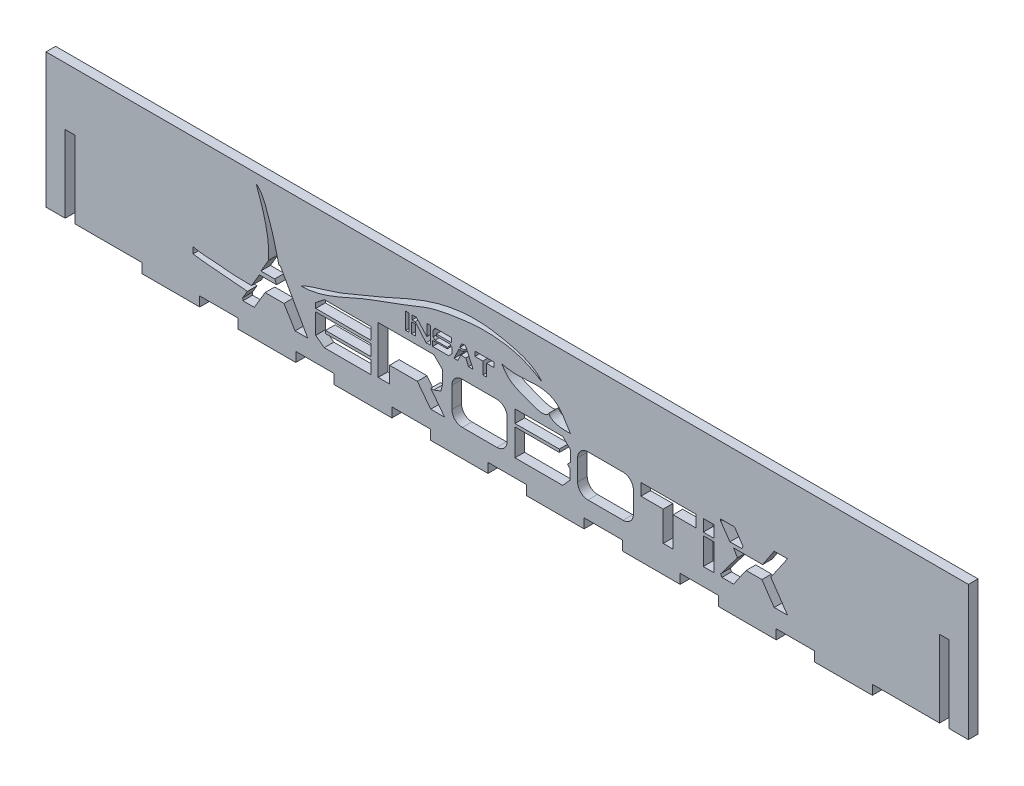
SolidWorks part; units mm, degrees
ref_plane "Front Plane" through (0, 0, 0) normal (0, 0, 1) x (1, 0, 0)
ref_plane "Top Plane" through (0, 0, 0) normal (0, 1, 0) x (1, 0, 0)
ref_plane "Right Plane" through (0, 0, 0) normal (1, 0, 0) x (0, 0, -1)
sketch "Sketch1" plane through (0, 0, 0) normal (0, 0, 1) x (1, 0, 0)
  line L17 (-145.2465, -47.102) -> (-145.2465, -36.1893)
  line L18 (-216.0657, -38.5489) -> (-244.8855, -38.5489)
  line L19 (-244.8855, -38.5489) -> (-244.8855, -49.141)
  line L20 (-244.8855, -49.141) -> (-240.4602, -52.4866)
  line L21 (-240.4602, -52.4866) -> (-216.0657, -52.4866)
  line L22 (-216.0657, -52.4866) -> (-216.0657, -45.7953)
  line L23 (-216.0657, -45.7953) -> (-239.7964, -45.7953)
  line L24 (-239.7964, -45.7953) -> (-239.7964, -44.3571)
  line L25 (-239.7964, -44.3571) -> (-216.0657, -44.3571)
  line L26 (-216.0657, -44.3571) -> (-216.0657, -38.5489)
  line L27 (-150.6312, -30.8046) -> (-168.6155, -30.8046)
  line L28 (-174.0001, -36.1893) -> (-174.0001, -47.102)
  line L29 (-168.6155, -52.4866) -> (-150.6312, -52.4866)
  line L33 (14.7535, -61.5468) -> (14.7535, -66.5468)
  line L34 (14.7535, -66.5468) -> (44.7535, -66.5468)
  line L35 (44.7535, -66.5468) -> (44.7535, -61.5468)
  line L37 (-35.2465, -61.5468) -> (-35.2465, -66.5468)
  line L38 (-35.2465, -66.5468) -> (-5.2465, -66.5468)
  line L39 (-5.2465, -66.5468) -> (-5.2465, -61.5468)
  line L41 (-85.2465, -61.5468) -> (-85.2465, -66.5468)
  line L42 (-85.2465, -66.5468) -> (-55.2465, -66.5468)
  line L43 (-55.2465, -66.5468) -> (-55.2465, -61.5468)
  line L45 (-135.2465, -61.5468) -> (-135.2465, -66.5468)
  line L46 (-135.2465, -66.5468) -> (-105.2465, -66.5468)
  line L47 (-105.2465, -66.5468) -> (-105.2465, -61.5468)
  line L49 (-185.2465, -61.5468) -> (-185.2465, -66.5468)
  line L50 (-185.2465, -66.5468) -> (-155.2465, -66.5468)
  line L51 (-155.2465, -66.5468) -> (-155.2465, -61.5468)
  line L53 (-235.2465, -61.5468) -> (-235.2465, -66.5468)
  line L54 (-235.2465, -66.5468) -> (-205.2465, -66.5468)
  line L55 (-205.2465, -66.5468) -> (-205.2465, -61.5468)
  line L57 (-285.2465, -61.5468) -> (-285.2465, -66.5468)
  line L58 (-285.2465, -66.5468) -> (-255.2465, -66.5468)
  line L59 (-255.2465, -66.5468) -> (-255.2465, -61.5468)
  line L61 (-335.2465, -61.5468) -> (-335.2465, -66.5468)
  line L62 (-335.2465, -66.5468) -> (-305.2465, -66.5468)
  line L63 (-305.2465, -66.5468) -> (-305.2465, -61.5468)
  line L64 (-335.2465, -61.5468) -> (-370.2465, -61.5468)
  line L65 (-370.2465, -61.5468) -> (-370.2465, -21.5468)
  line L66 (-370.2465, -21.5468) -> (-375.2465, -21.5468)
  line L67 (-375.2465, -21.5468) -> (-375.2465, -61.5468)
  line L68 (-375.2465, -61.5468) -> (-385.2465, -61.5468)
  line L69 (-385.2465, -61.5468) -> (-385.2465, 8.4532)
  line L70 (-385.2465, 8.4532) -> (94.7535, 8.4532)
  line L71 (-145.2465, -61.5468) -> (-145.2465, -97.7003) construction
  line L72 (-370.2465, -61.5468) -> (-335.2465, -61.5468)
  line L73 (-305.2465, -61.5468) -> (-285.2465, -61.5468)
  line L74 (-255.2465, -61.5468) -> (-235.2465, -61.5468)
  line L75 (-205.2465, -61.5468) -> (-185.2465, -61.5468)
  line L76 (-155.2465, -61.5468) -> (-135.2465, -61.5468)
  line L77 (-105.2465, -61.5468) -> (-85.2465, -61.5468)
  line L78 (-55.2465, -61.5468) -> (-35.2465, -61.5468)
  line L79 (-5.2465, -61.5468) -> (14.7535, -61.5468)
  line L80 (44.7535, -61.5468) -> (79.7535, -61.5468)
  line L81 (94.7535, -61.5468) -> (94.7535, 8.4532)
  line L82 (84.7535, -61.5468) -> (94.7535, -61.5468)
  line L83 (84.7535, -21.5468) -> (84.7535, -61.5468)
  line L84 (79.7535, -21.5468) -> (84.7535, -21.5468)
  line L85 (79.7535, -61.5468) -> (79.7535, -21.5468)
  line L90 (-216.0657, -30.8046) -> (-240.4602, -30.8046)
  line L91 (-216.0657, -37.0001) -> (-216.0657, -30.8046)
  line L92 (-244.8855, -37.0001) -> (-216.0657, -37.0001)
  line L93 (-244.8855, -34.3936) -> (-244.8855, -37.0001)
  line L94 (-240.4602, -30.8046) -> (-244.8855, -34.3936)
  line L120 (-177.8195, -52.4866) -> (-185.0448, -43.0192)
  line L121 (-185.0448, -52.4866) -> (-177.8195, -52.4866)
  line L122 (-191.99, -43.3863) -> (-185.0448, -52.4866)
  line L123 (-206.4528, -43.3863) -> (-191.99, -43.3863)
  line L124 (-206.4528, -51.837) -> (-206.4528, -43.3863)
  line L125 (-212.3742, -51.837) -> (-206.4528, -51.837)
  line L126 (-212.3742, -36.5353) -> (-212.3742, -51.837)
  line L127 (-212.3742, -34.3936) -> (-212.3742, -36.5353)
  line L128 (-212.3742, -27.0967) -> (-212.3742, -34.3936)
  line L129 (-183.4051, -27.0967) -> (-212.3742, -27.0967)
  line L130 (-178.9604, -31.5413) -> (-183.4051, -27.0967)
  line L131 (-178.9604, -38.5489) -> (-178.9604, -31.5413)
  line L132 (-179.7612, -41.6672) -> (-178.9604, -38.5489)
  line L133 (-183.4051, -43.0192) -> (-179.7612, -41.6672)
  line L134 (-185.0448, -43.0192) -> (-183.4051, -43.0192)
  line L141 (-108.6052, -36.1893) -> (-108.6052, -47.102)
  line L142 (-84.9481, -30.8046) -> (-103.2206, -30.8046)
  line L143 (-79.5635, -47.102) -> (-79.5635, -36.1893)
  line L144 (-103.2206, -52.4866) -> (-84.9481, -52.4866)
  line L146 (-141.1873, -52.4866) -> (-116.3332, -52.4866)
  line L147 (-116.3332, -52.4866) -> (-112.4985, -48.1336)
  line L148 (-112.4985, -48.1336) -> (-112.4985, -43.103)
  line L149 (-112.4985, -43.103) -> (-113.9344, -41.6672)
  line L150 (-113.9344, -41.6672) -> (-112.3546, -40.0875)
  line L151 (-112.3546, -40.0875) -> (-112.3546, -34.3936)
  line L152 (-112.3546, -34.3936) -> (-116.3332, -30.4151)
  line L153 (-116.3332, -30.4151) -> (-141.1873, -30.4151)
  line L154 (-141.1873, -30.4151) -> (-141.1873, -37.0001)
  line L155 (-141.1873, -37.0001) -> (-118.1322, -37.0001)
  line L156 (-118.1322, -37.0001) -> (-118.1322, -38.5489)
  line L157 (-118.1322, -38.5489) -> (-141.1873, -38.5489)
  line L158 (-141.1873, -38.5489) -> (-141.1873, -52.4866)
  line L164 (43.215, 8.4532) -> (-333.7081, 8.4532)
  line L170 (-37.7505, -38.5489) -> (-43.2161, -38.5489)
  line L171 (-43.2161, -38.5489) -> (-43.2161, -52.4866)
  line L172 (-43.2161, -52.4866) -> (-37.7505, -52.4866)
  line L173 (-37.7505, -52.4866) -> (-37.7505, -38.5489)
  line L178 (-100.6224, -45.7953) -> (-87.6214, -45.7953)
  line L179 (-103.3147, -39.6924) -> (-103.3147, -43.103)
  line L180 (-87.6214, -37.0001) -> (-100.6224, -37.0001)
  line L181 (-84.9291, -43.103) -> (-84.9291, -39.6924)
  line L194 (-64.0465, -52.4866) -> (-58.9306, -52.4866)
  line L195 (-58.9306, -52.4866) -> (-58.9306, -37.0001)
  line L196 (-58.9306, -37.0001) -> (-47.0741, -37.0001)
  line L197 (-47.0741, -37.0001) -> (-47.0741, -30.8046)
  line L198 (-47.0741, -30.8046) -> (-75.6692, -30.8046)
  line L199 (-75.6692, -30.8046) -> (-75.6692, -37.0001)
  line L200 (-75.6692, -37.0001) -> (-64.0465, -37.0001)
  line L201 (-64.0465, -37.0001) -> (-64.0465, -52.4866)
  line L202 (-37.7505, -37.0001) -> (-37.7505, -30.8046)
  line L203 (-43.2161, -37.0001) -> (-37.7505, -37.0001)
  line L204 (-43.2161, -30.8046) -> (-43.2161, -37.0001)
  line L205 (-37.7505, -30.8046) -> (-43.2161, -30.8046)
  line L214 (-23.105, -34.3936) -> (-22.5719, -32.9503)
  line L215 (-22.5719, -32.9503) -> (-26.9458, -26.5103)
  line L216 (-26.9458, -26.5103) -> (-34.1401, -26.5103)
  line L217 (-34.1401, -26.5103) -> (-34.1401, -27.5707)
  line L218 (-34.1401, -27.5707) -> (-29.3423, -34.3936)
  line L219 (-29.3423, -34.3936) -> (-23.105, -34.3936)
  line L235 (-192.8734, -23.5064) -> (-192.8734, -18.0283)
  line L236 (-195, -23.5064) -> (-192.8734, -23.5064)
  line L237 (-195, -18.0283) -> (-195, -23.5064)
  line L238 (-192.8734, -18.0283) -> (-195, -18.0283)
  line L240 (-27.4231, -36.1893) -> (-25.4506, -39.6924)
  line L241 (-12.3365, -36.1893) -> (-27.4231, -36.1893)
  line L242 (-6.3125, -27.0967) -> (-12.3365, -36.1893)
  line L243 (0.6178, -27.0967) -> (-6.3125, -27.0967)
  line L244 (-8.0717, -39.6924) -> (0.6178, -27.0967)
  line L245 (0.6178, -52.4866) -> (-8.0717, -39.6924)
  line L246 (-6.3125, -52.4866) -> (0.6178, -52.4866)
  line L247 (-12.6855, -43.103) -> (-6.3125, -52.4866)
  line L248 (-20.9285, -43.103) -> (-12.6855, -43.103)
  line L249 (-27.4231, -52.5172) -> (-20.9285, -43.103)
  line L250 (-33.5004, -52.5172) -> (-27.4231, -52.5172)
  line L251 (-34.1401, -51.2137) -> (-33.5004, -52.5172)
  line L252 (-25.4506, -39.6924) -> (-34.1401, -51.2137)
  line L256 (-136.2442, -44.0282) -> (-136.2442, -46.2384)
  line L257 (-117.6988, -44.0282) -> (-136.2442, -44.0282)
  line L258 (-117.6988, -46.2384) -> (-117.6988, -44.0282)
  line L259 (-136.2442, -46.2384) -> (-117.6988, -46.2384)
  line L264 (-198.0808, -23.5064) -> (-196.2541, -23.5064)
  line L265 (-196.2541, -23.5064) -> (-196.2541, -14.8111)
  line L266 (-196.2541, -14.8111) -> (-198.0808, -14.8111)
  line L267 (-198.0808, -14.8111) -> (-198.0808, -23.5064)
  line L296 (-308.7385, -41.0793) -> (-308.7385, -44.3571)
  line L297 (-277.2448, -41.6672) -> (-278.2599, -43.3863)
  line L298 (-274.2146, -36.5353) -> (-277.2448, -41.6672)
  line L299 (-265.2435, -36.5353) -> (-274.2146, -36.5353)
  line L300 (-266.2436, -34.3936) -> (-265.2435, -36.5353)
  line L301 (-273.4262, -34.3936) -> (-266.2436, -34.3936)
  line L302 (-269.3974, -27.5707) -> (-273.4262, -34.3936)
  line L303 (-263.2888, -27.0967) -> (-264.038, -27.0967)
  line L304 (-249.0379, -52.4866) -> (-263.2888, -27.0967)
  line L305 (-255.6091, -52.4866) -> (-249.0379, -52.4866)
  line L306 (-261.4222, -43.0192) -> (-255.6091, -52.4866)
  line L307 (-271.2362, -43.0192) -> (-261.4222, -43.0192)
  line L308 (-276.8264, -52.4866) -> (-271.2362, -43.0192)
  line L309 (-282.7655, -52.4866) -> (-276.8264, -52.4866)
  line L310 (-282.8818, -51.2137) -> (-282.7655, -52.4866)
  line L311 (-280.4539, -47.102) -> (-282.8818, -51.2137)
  line L314 (-194.7274, -17.1286) -> (-193.0915, -17.1286)
  line L315 (-194.7274, -14.8111) -> (-194.7274, -17.1286)
  line L316 (-192.5296, -14.8111) -> (-194.7274, -14.8111)
  line L317 (-187.039, -20.7819) -> (-192.5296, -14.8111)
  line L318 (-187.039, -14.8111) -> (-187.039, -20.7819)
  line L319 (-185.0448, -14.8111) -> (-187.039, -14.8111)
  line L320 (-185.0448, -23.7264) -> (-185.0448, -14.8111)
  line L321 (-187.4752, -23.7264) -> (-185.0448, -23.7264)
  line L322 (-193.0915, -17.1286) -> (-187.4752, -23.7264)
  line L346 (-175.1382, -18.1089) -> (-182.1193, -18.1089)
  line L347 (-182.1193, -18.1089) -> (-182.1193, -17.1286)
  line L348 (-182.1193, -17.1286) -> (-174.3118, -17.1286)
  line L349 (-174.3118, -17.1286) -> (-174.3118, -14.8111)
  line L350 (-174.3118, -14.8111) -> (-182.8169, -14.8111)
  line L351 (-182.8169, -14.8111) -> (-183.8096, -16.242)
  line L352 (-183.8096, -16.242) -> (-183.8096, -19.3006)
  line L353 (-183.8096, -19.3006) -> (-182.8169, -20.2933)
  line L354 (-182.8169, -20.2933) -> (-176.4428, -20.2933)
  line L355 (-176.4428, -20.2933) -> (-176.4428, -20.9909)
  line L356 (-176.4428, -20.9909) -> (-184.0779, -20.9909)
  line L357 (-184.0779, -20.9909) -> (-184.0779, -23.7264)
  line L358 (-184.0779, -23.7264) -> (-175.6264, -23.7264)
  line L359 (-175.6264, -23.7264) -> (-174.0001, -21.9881)
  line L360 (-174.0001, -21.9881) -> (-174.0968, -19.0833)
  line L361 (-174.0968, -19.0833) -> (-175.1382, -18.1089)
  line L362 (-162.0596, -17.214) -> (-157.9211, -17.214)
  line L363 (-162.0596, -14.8111) -> (-162.0596, -17.214)
  line L364 (-152.0122, -14.8111) -> (-162.0596, -14.8111)
  line L365 (-152.0122, -17.2995) -> (-152.0122, -14.8111)
  line L366 (-155.9305, -17.2995) -> (-152.0122, -17.2995)
  line L367 (-155.9305, -23.5064) -> (-155.9305, -17.2995)
  line L368 (-157.9211, -23.5064) -> (-155.9305, -23.5064)
  line L369 (-157.9211, -17.214) -> (-157.9211, -23.5064)
  line L386 (-170.3775, -18.1089) -> (-172.8979, -23.5064)
  line L387 (-167.6809, -18.1089) -> (-170.3775, -18.1089)
  line L388 (-167.6809, -17.1286) -> (-167.6809, -18.1089)
  line L389 (-169.9713, -17.1286) -> (-167.6809, -17.1286)
  line L390 (-168.8261, -14.8111) -> (-169.9713, -17.1286)
  line L391 (-166.9174, -14.8111) -> (-168.8261, -14.8111)
  line L392 (-163.0046, -23.5064) -> (-166.9174, -14.8111)
  line L393 (-165.3586, -23.5064) -> (-163.0046, -23.5064)
  line L394 (-166.8045, -20.2933) -> (-165.3586, -23.5064)
  line L395 (-169.3987, -20.2933) -> (-166.8045, -20.2933)
  line L396 (-170.9865, -23.5064) -> (-169.3987, -20.2933)
  line L397 (-172.8979, -23.5064) -> (-170.9865, -23.5064)
  arc A8 (-145.2465, -36.1893) -> (-150.6312, -30.8046) centre (-150.6312, -36.1893) ccw
  arc A9 (-168.6155, -30.8046) -> (-174.0001, -36.1893) centre (-168.6155, -36.1893) ccw
  arc A10 (-174.0001, -47.102) -> (-168.6155, -52.4866) centre (-168.6155, -47.102) ccw
  arc A11 (-150.6312, -52.4866) -> (-145.2465, -47.102) centre (-150.6312, -47.102) ccw
  arc A16 (-108.6052, -47.102) -> (-103.2206, -52.4866) centre (-103.2206, -47.102) ccw
  arc A17 (-103.2206, -30.8046) -> (-108.6052, -36.1893) centre (-103.2206, -36.1893) ccw
  arc A18 (-79.5635, -36.1893) -> (-84.9481, -30.8046) centre (-84.9481, -36.1893) ccw
  arc A19 (-84.9481, -52.4866) -> (-79.5635, -47.102) centre (-84.9481, -47.102) ccw
  arc A24 (-87.6214, -45.7953) -> (-84.9291, -43.103) centre (-87.6214, -43.103) ccw
  arc A25 (-103.3147, -43.103) -> (-100.6224, -45.7953) centre (-100.6224, -43.103) ccw
  arc A26 (-100.6224, -37.0001) -> (-103.3147, -39.6924) centre (-100.6224, -39.6924) ccw
  arc A27 (-84.9291, -39.6924) -> (-87.6214, -37.0001) centre (-87.6214, -39.6924) ccw
  spline S6 degree 3 poles (-148.1186, -13.43) (-147.0364, -15.2629) (-143.8631, -19.8587) (-136.1557, -22.3385) (-129.6979, -25.2904) (-124.4191, -25.5853) (-123.5271, -23.5064) knots 0 0 0 0 0.222563 0.555789 0.790592 1 1 1 1
  spline S7 degree 3 poles (-123.5271, -23.5064) (-123.1635, -24.9575) (-119.3489, -27.1713) (-115.1325, -27.2555) (-112.3546, -27.0967) knots 0 0 0 0 0.328242 1 1 1 1
  spline S8 degree 3 poles (-112.3546, -27.0967) (-114.7105, -23.5048) (-117.744, -16.8788) (-127.4658, -13.646) (-136.8137, -14.6731) (-144.2603, -14.7043) (-148.1186, -13.43) knots 0 0 0 0 0.326564 0.464231 0.711528 1 1 1 1
  spline S10 degree 3 poles (-252.81, -30.8046) (-240.7613, -30.5476) (-224.4445, -20.9196) (-201.9469, -13.9742) (-186.0425, -6.7269) (-171.9566, -4.2168) (-160.3472, -2.8975) (-150.5444, -3.1278) (-139.4318, -4.709) (-131.3676, -8.5816) (-126.9869, -11.3833) knots 0 0 0 0 0.263229 0.423654 0.534863 0.658763 0.746702 0.800187 0.881407 1 1 1 1
  spline S11 degree 3 poles (-126.9869, -11.3833) (-131.4852, -5.9854) (-142.6017, -2.674) (-160.7812, 0.5343) (-177.2789, -1.4122) (-194.3674, -7.2169) (-206.7687, -13.2263) (-221.3138, -19.1399) (-235.3118, -25.468) (-247.4793, -28.074) (-252.81, -30.8046) knots 0 0 0 0 0.150329 0.252439 0.414342 0.514799 0.6567 0.722771 0.867027 1 1 1 1
  spline S18 degree 3 poles (-278.2599, -43.3863) (-282.1646, -43.4795) (-288.805, -43.2136) (-298.9497, -42.1505) (-305.2544, -41.9571) (-308.7385, -41.0793) knots 0 0 0 0 0.382817 0.650677 1 1 1 1
  spline S19 degree 3 poles (-275.9392, 3.7987) (-273.6701, -2.1306) (-270.1912, -12.3897) (-269.1332, -23.1719) (-269.3974, -27.5707) knots 0 0 0 0 0.591156 1 1 1 1
  spline S20 degree 3 poles (-264.038, -27.0967) (-265.2743, -22.9237) (-266.4722, -16.4254) (-269.8119, -7.1459) (-271.917, -0.4639) (-274.9523, 2.9795) (-275.9392, 3.7987) knots 0 0 0 0 0.38821 0.583927 0.882923 0.993987 0.993987 0.993987 0.993987
  spline S21 degree 3 poles (-308.7385, -44.3571) (-304.2159, -45.0828) (-294.7682, -45.8096) (-285.3261, -46.582) (-280.4539, -47.102) knots 0 0 0 0 0.482839 1 1 1 1
  point P23 (-145.2465, 8.4532)
  dimension "D1" = 70
  dimension "D2" = 40
  dimension "D3" = 5
  dimension "D4" = 35
  dimension "D5" = 10
extrude "Boss-Extrude1" add sketch "Sketch1" along normal blind 5 contours L70 L71 L76 L45 L46 L47 L77 L41 L42 L43 L78 L37 L38 L39 L79 L33 L34 L35 L80 L85 L84 L83 L82 L81 | L71 L70 L69 L68 L67 L66 L65 L64 L61 L62 L63 L73 L57 L58 L59 L74 L53 L54 L55 L75 L49 L50 L51 L76 region at (-143.77, -26.1907, 0)
